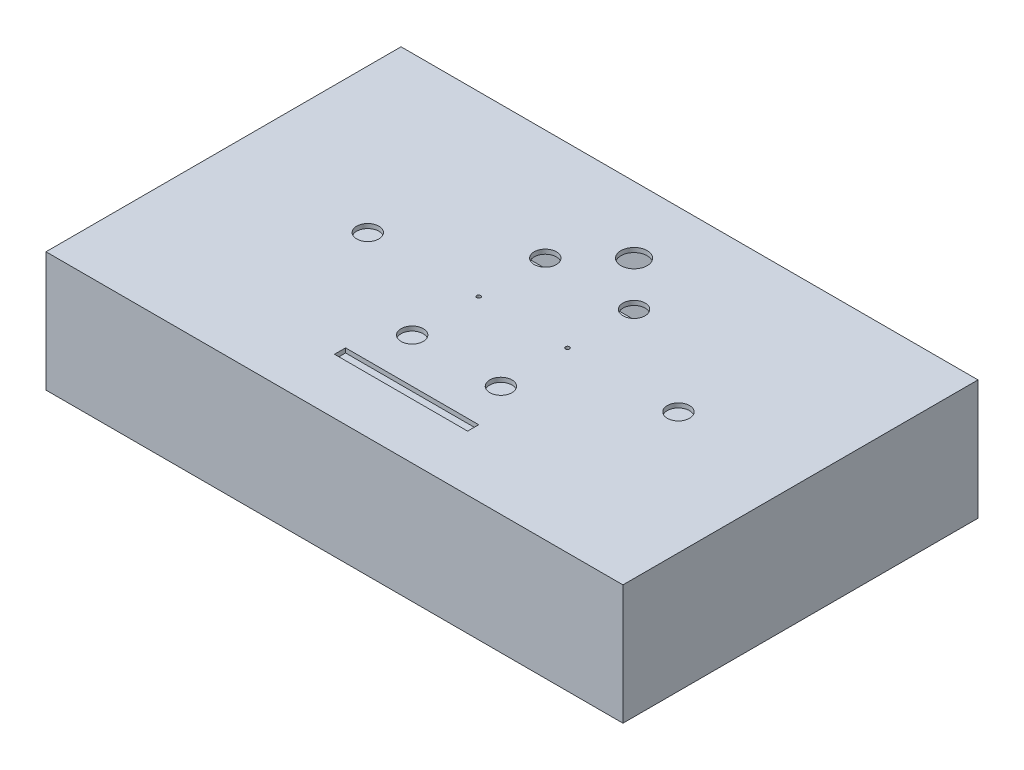
SolidWorks part; units mm, degrees
ref_plane "Front Plane" through (0, 0, 0) normal (0, 0, 1) x (1, 0, 0)
ref_plane "Top Plane" through (0, 0, 0) normal (0, 1, 0) x (1, 0, 0)
ref_plane "Right Plane" through (0, 0, 0) normal (1, 0, 0) x (0, 0, -1)
sketch "Sketch1" plane through (0, 0, 0) normal (0, 1, 0) x (1, 0, 0)
  line L1 (-171.45, 101.6) -> (158.75, 101.6)
  line L2 (-171.45, 101.6) -> (-171.45, -101.6)
  line L3 (-171.45, -101.6) -> (158.75, -101.6)
  line L4 (158.75, 101.6) -> (158.75, -101.6)
  dimension "D1" = 330.2
  dimension "D2" = 203.2
  dimension "D3" = 101.6
  dimension "D4" = 171.45
extrude "Boss-Extrude1" add sketch "Sketch1" along normal blind 68.58
shell "Shell1" thickness 2.54
sketch "Sketch3" plane through (0, 68.58, 0) normal (0, 1, 0) x (1, 0, 0)
  line L0 (0, -37.719) -> (0, 37.719) construction
  circle A0 centre (-88.9, 0) radius 6.35
  circle A1 centre (88.9, 0) radius 6.35
  dimension "D1" = 12.7
  dimension "D2" = 12.7
  dimension "D3" = 88.9
  dimension "D4" = 88.9
extrude "Cut-Extrude1" cut sketch "Sketch3" against normal blind 2.54
hole_wizard "#4-40 Tapped Hole1" positions "Sketch9" profile "Sketch8" tap size "#4-40" standard "ANSI Inch" end condition up to next
sketch "Sketch9" plane through (0, 68.58, 0) normal (0, 1, 0) x (1, 0, 0)
  line L0 (0, -37.719) -> (0, 37.719) construction
  point P0 (-25.4, 0)
  point P2 (25.4, 0)
  dimension "D1" = 25.4
  dimension "D2" = 25.4
sketch "Sketch8" plane through (-25.4, 68.58, 0) normal (1, 0, 0) x (0, 0, 1)
  line L0 (0, 0) -> (0, 2.54)
  line L1 (0, 2.54) -> (1.1303, 2.54)
  line L2 (1.1303, 2.54) -> (1.1303, 0)
  line L5 (1.1303, 0) -> (0, 0)
  line L11 (0, -6.35) -> (0, 107.95) construction
  dimension "Thread Major Dia." = 2.2606
  dimension "Thru Tap Drill Depth" = 2.54
sketch "Sketch10" plane through (0, 68.58, 0) normal (0, 1, 0) x (1, 0, 0)
  line L1 (-29.0322, 16.1544) -> (29.0322, 16.1544)
  line L2 (-29.0322, 16.1544) -> (-29.0322, -16.1544)
  line L3 (-29.0322, -16.1544) -> (29.0322, -16.1544)
  line L4 (29.0322, 16.1544) -> (29.0322, -16.1544)
  dimension "D1" = 16.1544
  dimension "D2" = 32.3088
  dimension "D3" = 29.0322
  dimension "D4" = 58.0644
sketch "Sketch11" plane through (0, 68.58, 0) normal (0, 1, 0) x (1, 0, 0)
  line L0 (0, -37.719) -> (0, 37.719) construction
  line L1 (-37.719, 0) -> (37.719, 0) construction
  circle A0 centre (-25.4, 38.1) radius 6.35
  circle A1 centre (25.4, 38.1) radius 6.35
  circle A2 centre (25.4, -38.1) radius 6.35
  circle A3 centre (-25.4, -38.1) radius 6.35
  dimension "D1" = 12.7
  dimension "D2" = 25.4
  dimension "D3" = 25.4
  dimension "D4" = 38.1
  dimension "D5" = 76.2
extrude "Cut-Extrude2" cut sketch "Sketch11" against normal blind 2.54
sketch "Sketch12" plane through (0, 68.58, 0) normal (0, 1, 0) x (1, 0, 0)
  line L0 (-37.719, 0) -> (37.719, 0) construction
  line L2 (-38.1, -63.5) -> (38.1, -63.5)
  line L3 (-38.1, -63.5) -> (-38.1, -69.85)
  line L4 (-38.1, -69.85) -> (38.1, -69.85)
  line L5 (38.1, -63.5) -> (38.1, -69.85)
  circle A0 centre (0, 63.5) radius 7.5032
  dimension "D1" = 63.5
  dimension "D2" = 63.5
  dimension "D3" = 6.35
  dimension "D4" = 76.2
  dimension "D5" = 38.1
extrude "Cut-Extrude3" cut sketch "Sketch12" against normal blind 2.54
